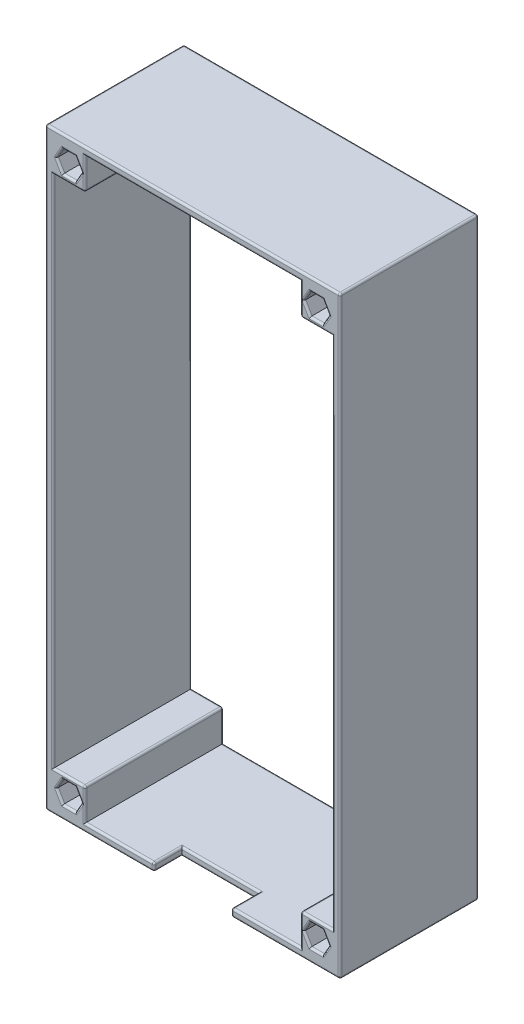
SolidWorks part; units mm, degrees
note: The reader was unsure of these and kept them because the rebuilt part matched: shared geometry of "Sketch1<3>", "Sketch1<4>".
ref_plane "Front Plane" through (0, 0, 0) normal (0, 0, 1) x (1, 0, 0)
ref_plane "Top Plane" through (0, 0, 0) normal (0, 1, 0) x (1, 0, 0)
ref_plane "Right Plane" through (0, 0, 0) normal (1, 0, 0) x (0, 0, -1)
sketch "Sketch1" plane through (0, 0, 0) normal (0, 0, 1) x (1, 0, 0)
  line L0 (-35.25, -37.5) -> (-35.25, 35.5)
  line L1 (37.25, -37.5) -> (-37.25, -37.5)
  line L2 (37.25, -37.5) -> (37.25, 37.5)
  line L3 (37.25, 37.5) -> (-37.25, 37.5)
  line L4 (-37.25, -37.5) -> (-37.25, 37.5)
  line L5 (0, 37.5) -> (0, -37.5) construction
  line L6 (37.25, 0) -> (-37.25, 0) construction
  line L7 (35.25, 35.5) -> (-35.25, 35.5)
  line L8 (35.25, -37.5) -> (35.25, 35.5)
  line L9 (-31.25, 35.5) -> (-31.25, 31.5) construction
  line L10 (-31.25, 31.5) -> (-35.25, 31.5) construction
  line L11 (35.25, 31.5) -> (31.25, 31.5) construction
  line L12 (31.25, 31.5) -> (31.25, 35.5) construction
  line L13 (-31.25, 31.5) -> (-27.25, 31.5) construction
  line L14 (28.0746, 31.5) -> (29.6623, 28.75)
  line L15 (29.6623, 28.75) -> (32.8377, 28.75)
  line L16 (32.8377, 28.75) -> (34.4254, 31.5)
  line L17 (34.4254, 31.5) -> (32.8377, 34.25)
  line L18 (32.8377, 34.25) -> (29.6623, 34.25)
  line L19 (29.6623, 34.25) -> (28.0746, 31.5)
  line L20 (-28.0746, 31.5) -> (-29.6623, 34.25)
  line L21 (-29.6623, 34.25) -> (-32.8377, 34.25)
  line L22 (-32.8377, 34.25) -> (-34.4254, 31.5)
  line L23 (-34.4254, 31.5) -> (-32.8377, 28.75)
  line L24 (-32.8377, 28.75) -> (-29.6623, 28.75)
  line L25 (-29.6623, 28.75) -> (-28.0746, 31.5)
  line L26 (-31.25, 31.5) -> (-31.25, 27.5) construction
  line L27 (31.25, 31.5) -> (31.25, 27.5) construction
  line L28 (31.25, 31.5) -> (27.25, 31.5) construction
  line L29 (27.25, 31.5) -> (27.25, 35.5)
  line L30 (27.25, 31.5) -> (27.25, 27.5)
  line L31 (27.25, 27.5) -> (31.25, 27.5)
  line L32 (31.25, 27.5) -> (35.25, 27.5)
  line L33 (-31.25, 27.5) -> (-35.25, 27.5)
  line L34 (-31.25, 27.5) -> (-27.25, 27.5)
  line L35 (-27.25, 27.5) -> (-27.25, 31.5)
  line L36 (-27.25, 31.5) -> (-27.25, 35.5)
  circle A0 centre (31.25, 31.5) radius 1.75
  circle A1 centre (31.25, 31.5) radius 2.75 construction
  circle A2 centre (-31.25, 31.5) radius 1.75
  circle A3 centre (-31.25, 31.5) radius 2.75 construction
  point P0 (0, 0)
  dimension "D8" = 3.5
  dimension "D9" = 5.5
  dimension "D1" = 74.5
  dimension "D2" = 75
  dimension "D5" = 4
  dimension "D6" = 4
  dimension "D3" = 2
extrude "Boss-Extrude3" add sketch "Sketch1" along normal blind 35 contours L8 L1 L2 L3 L4 L0 L7
extrude "Boss-Extrude4" add sketch "Sketch1<3>" along normal up to surface (35 mm away) contours L35 L36 L7 L0 L33 L34 L25 L24 L23 L22 L21 L20 | L31 L32 L8 L7 L29 L30 L19 L18 L17 L16 L15 L14 up to face at (0, -0.5, 35)
sketch "Sketch1<3>" plane through (0, 0, 0) normal (0, 0, 1) x (1, 0, 0) same geometry as "Sketch1"
extrude "Boss-Extrude5" add sketch "Sketch1<4>" along normal blind 29.7 contours L18 L19 L14 L15 L16 L17 A0 | L24 L25 L20 L21 L22 L23 A2
sketch "Sketch1<4>" plane through (0, 0, 0) normal (0, 0, 1) x (1, 0, 0) same geometry as "Sketch1"
mirror "Mirror1" about plane through (0, -37.5, 35) normal (0, -1, 0) of bodies 105
sketch "Sketch8" plane through (0, -112.5, 0) normal (0, -1, 0) x (1, 0, 0)
  line L0 (0, 35) -> (-9.75, 35)
  line L1 (37.25, 35) -> (-37.25, 35) construction
  line L2 (-9.75, 35) -> (-9.75, 28)
  line L3 (-9.75, 28) -> (9.75, 28)
  line L4 (9.75, 28) -> (9.75, 35)
  line L5 (9.75, 35) -> (0, 35)
  dimension "D1" = 7
  dimension "D2" = 19.5
extrude "Cut-Extrude2" cut sketch "Sketch8" against normal blind 10
fillet "Fillet2" radius 0.5 78 edges at (-35.25, -37.5, 0) (-29.5, 31.5, 0) (-37.25, -37.5, 0) (0, 37.5, 0) (37.25, -37.5, 0) (35.25, -37.5, 0) (0, -110.5, 0) (37.25, -112.5, 17.5) (23.5, -112.5, 35) (-37.25, -112.5, 17.5) (27.25, -106.5, 35) (18.5, -110.5, 35) (-31.25, -102.5, 35) (28.8684, -107.875, 35) (28.8684, -105.125, 35) (31.25, -103.75, 35) (33.6316, -105.125, 35) (33.6316, -107.875, 35) (31.25, -109.25, 35) (-28.8684, -105.125, 35) (-28.8684, -107.875, 35) (-31.25, -109.25, 35) (-33.6316, -107.875, 35) (-33.6316, -105.125, 35) (-31.25, -103.75, 35) (0, -112.5, 0) (-27.25, -106.5, 0) (31.25, -102.5, 0) (27.25, -102.5, 17.5) (27.25, -106.5, 0) (31.25, -102.5, 35) (-27.25, -102.5, 17.5) (-31.25, -102.5, 0) (-27.25, -106.5, 35) (-29.5, -106.5, 0) (33, -106.5, 0) (37.25, -37.5, 35) (-37.25, 37.5, 17.5) (37.25, 37.5, 17.5) (-23.5, -112.5, 35) (-18.5, -110.5, 35) (-9.75, -110.5, 31.5) (9.75, -110.5, 31.5) (-9.75, -111.5, 35) (0, -110.5, 28) (9.75, -111.5, 35) (9.75, -112.5, 31.5) (-9.75, -112.5, 31.5) (0, -112.5, 28) (0, 37.5, 35) (-37.25, -37.5, 35) (0, 35.5, 0) (0, 35.5, 35) (-28.8684, 32.875, 35) (-31.25, 34.25, 35) (-33.6316, 32.875, 35) (-33.6316, 30.125, 35) (-31.25, 28.75, 35) (-28.8684, 30.125, 35) (-35.25, -37.5, 35) (-31.25, 27.5, 0) (-31.25, 27.5, 35) (-27.25, 27.5, 17.5) (-27.25, 31.5, 0) (-27.25, 31.5, 35) (28.8684, 30.125, 35) (31.25, 28.75, 35) (33.6316, 30.125, 35) (33.6316, 32.875, 35) (31.25, 34.25, 35) (28.8684, 32.875, 35) (27.25, 31.5, 0) (27.25, 31.5, 35) (27.25, 27.5, 17.5) (31.25, 27.5, 0) (31.25, 27.5, 35) (35.25, -37.5, 35) (33, 31.5, 0)
